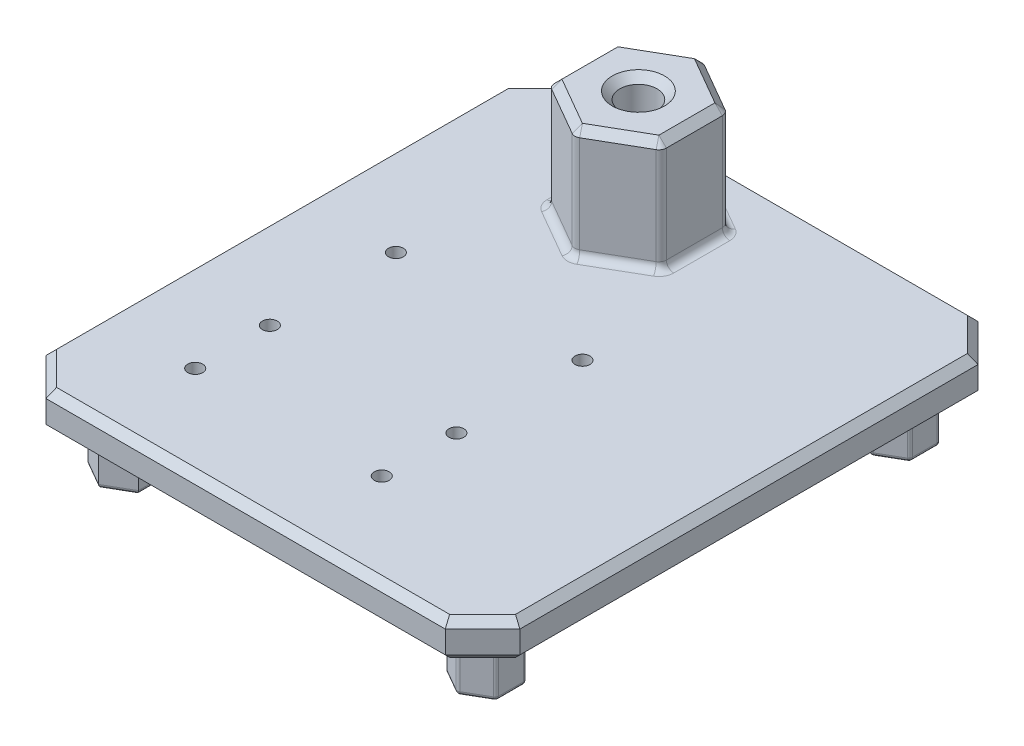
SolidWorks part; units mm, degrees
ref_plane "Front Plane" through (0, 0, 0) normal (0, 0, 1) x (1, 0, 0)
ref_plane "Top Plane" through (0, 0, 0) normal (0, 1, 0) x (1, 0, 0)
ref_plane "Right Plane" through (0, 0, 0) normal (1, 0, 0) x (0, 0, -1)
sketch "Sketch2" plane through (0, 0, 0) normal (0, 1, 0) x (1, 0, 0)
  line L1 (0, -17.3205) -> (15, -8.6603)
  line L2 (15, -8.6603) -> (15, 8.6603)
  line L3 (15, 8.6603) -> (0, 17.3205)
  line L4 (0, 17.3205) -> (-15, 8.6603)
  line L5 (-15, 8.6603) -> (-15, -8.6603)
  line L6 (-15, -8.6603) -> (0, -17.3205)
  circle A0 centre (0, 0) radius 15 construction
  circle A1 centre (0, 0) radius 5
  dimension "D2" = 10
  dimension "D1" = 30
extrude "Boss-Extrude1" add sketch "Sketch2" along normal blind 30
sketch "Sketch4" plane through (0, 0, 0) normal (0, 1, 0) x (1, 0, 0)
  line L0 (-40, 24.0027) -> (-50, 14.0027)
  line L1 (-40, 24.0027) -> (67.0218, 24.0027)
  line L2 (-50, 14.0027) -> (-50, -108.7974)
  line L3 (-40, -118.7974) -> (67.0218, -118.7974)
  line L4 (77.0218, 14.0027) -> (77.0218, -108.7974)
  line L5 (-50, 24.0027) -> (77.0218, -118.7974) construction
  line L6 (-50, -118.7974) -> (77.0218, 24.0027) construction
  line L7 (67.0218, 24.0027) -> (77.0218, 14.0027)
  line L8 (67.0218, -118.7974) -> (77.0218, -108.7974)
  line L9 (-50, -108.7974) -> (-40, -118.7974)
  point P0 (13.5109, -47.3973)
  dimension "D1" = 50
extrude "Boss-Extrude2" add sketch "Sketch4" against normal blind 10 contours L2 L9 L3 L8 L4 L7 L1 L0
sketch "Sketch5" plane through (0, 0, 0) normal (0, 1, 0) x (1, 0, 0)
  line L0 (-40, -118.7974) -> (67.0218, -118.7974) construction
  line L1 (-25, -93.7974) -> (-25, -7.9597) construction
  point P0 (-25, -40)
  point P1 (25, -40)
  point P4 (-25, -73.7974)
  point P6 (-25, -93.7974)
  point P8 (25, -73.7974)
  point P10 (25, -93.7974)
  dimension "D1" = 50
  dimension "D2" = 25
  dimension "D3" = 40
  dimension "D4" = 25
  dimension "D5" = 45
hole_wizard "Ø4.0mm Dowel Hole1" positions "Sketch5" profile "Sketch6" hole size "Ø4.0" standard "ISO"
sketch "Sketch6" plane through (-25, 0, 40) normal (1, 0, 0) x (0, 0, 1)
  line L0 (0, 0) -> (0, 11.2017)
  line L1 (0, 11.2017) -> (2, 10)
  line L2 (2, 10) -> (2, 0)
  line L5 (2, 0) -> (0, 0)
  line L10 (0, 11.2017) -> (-2, 10) construction
  line L11 (0, -6.35) -> (0, 107.95) construction
  dimension "Hole Dia." = 4
  dimension "Hole Depth" = 10
  dimension "Drill Angle" = 118
fillet "Fillet1" radius 2 12 edges at (-7.5, 0, -12.9904) (-15, 0, 0) (7.5, 0, -12.9904) (-7.5, 0, 12.9904) (15, 0, 0) (7.5, 0, 12.9904) (15, 15, -8.6603) (0, 15, -17.3205) (-15, 15, -8.6603) (-15, 15, 8.6603) (0, 15, 17.3205) (15, 15, 8.6603)
chamfer "Chamfer1" distance 2 angle 45 12 edges at (7.5, 30, -12.9904) (0, 30, -17.0111) (14.7321, 30, -8.5056) (-7.5, 30, -12.9904) (15, 30, 0) (-14.7321, 30, -8.5056) (14.7321, 30, 8.5056) (-15, 30, 0) (7.5, 30, 12.9904) (-14.7321, 30, 8.5056) (0, 30, 17.0111) (-7.5, 30, 12.9904)
chamfer "Chamfer2" distance 2 angle 45 1 edges at (0, 30, 5)
sketch "Sketch7" plane through (0, -10, 0) normal (0, -1, 0) x (1, 0, 0)
  line L0 (-50, -14.0027) -> (-50, 108.7974) construction
  line L1 (-28.25, -12.3225) -> (-28.25, -5.683)
  line L2 (-28.75, -4.8169) -> (-34.5, -1.4972)
  line L3 (-35.5, -1.4972) -> (-41.25, -4.8169)
  line L4 (-41.75, -5.683) -> (-41.75, -12.3225)
  line L5 (-41.25, -13.1885) -> (-35.5, -16.5083)
  line L6 (-34.5, -16.5083) -> (-28.75, -13.1885)
  line L7 (67.75, -12.3225) -> (67.75, -5.683)
  line L8 (67.25, -4.8169) -> (61.5, -1.4972)
  line L9 (60.5, -1.4972) -> (54.75, -4.8169)
  line L10 (54.25, -5.683) -> (54.25, -12.3225)
  line L11 (54.75, -13.1885) -> (60.5, -16.5083)
  line L12 (61.5, -16.5083) -> (67.25, -13.1885)
  line L13 (67.75, 98.5575) -> (67.75, 105.197)
  line L14 (67.25, 106.0631) -> (61.5, 109.3828)
  line L15 (60.5, 109.3828) -> (54.75, 106.0631)
  line L16 (54.25, 105.197) -> (54.25, 98.5575)
  line L17 (54.75, 97.6915) -> (60.5, 94.3717)
  line L18 (61.5, 94.3717) -> (67.25, 97.6915)
  line L19 (-40, -24.0027) -> (67.0218, -24.0027) construction
  line L21 (-35, 94.083) -> (-28.25, 97.9802)
  line L22 (-28.25, 97.9802) -> (-28.25, 105.7744)
  line L23 (-28.25, 105.7744) -> (-35, 109.6715)
  line L24 (-35, 109.6715) -> (-41.75, 105.7744)
  line L25 (-41.75, 105.7744) -> (-41.75, 97.9802)
  line L26 (-41.75, 97.9802) -> (-35, 94.083)
  circle A0 centre (-35, -9.0027) radius 6.75 construction
  circle A1 centre (61, -9.0027) radius 6.75 construction
  circle A2 centre (61, 101.8773) radius 6.75 construction
  arc A3 (67.75, 98.5575) -> (67.25, 97.6915) centre (66.75, 98.5575) cw
  arc A4 (60.5, 94.3717) -> (61.5, 94.3717) centre (61, 95.2377) ccw
  arc A5 (54.25, 98.5575) -> (54.75, 97.6915) centre (55.25, 98.5575) ccw
  arc A6 (54.75, 106.0631) -> (54.25, 105.197) centre (55.25, 105.197) ccw
  arc A7 (61.5, 109.3828) -> (60.5, 109.3828) centre (61, 108.5168) ccw
  arc A8 (67.75, -5.683) -> (67.25, -4.8169) centre (66.75, -5.683) ccw
  arc A9 (67.75, -12.3225) -> (67.25, -13.1885) centre (66.75, -12.3225) cw
  arc A10 (60.5, -16.5083) -> (61.5, -16.5083) centre (61, -15.6423) ccw
  arc A11 (54.25, -12.3225) -> (54.75, -13.1885) centre (55.25, -12.3225) ccw
  arc A12 (54.75, -4.8169) -> (54.25, -5.683) centre (55.25, -5.683) ccw
  arc A13 (61.5, -1.4972) -> (60.5, -1.4972) centre (61, -2.3632) ccw
  arc A14 (-28.25, -5.683) -> (-28.75, -4.8169) centre (-29.25, -5.683) ccw
  arc A15 (-28.25, -12.3225) -> (-28.75, -13.1885) centre (-29.25, -12.3225) cw
  arc A16 (-35.5, -16.5083) -> (-34.5, -16.5083) centre (-35, -15.6423) ccw
  arc A17 (-41.75, -12.3225) -> (-41.25, -13.1885) centre (-40.75, -12.3225) ccw
  arc A18 (-41.25, -4.8169) -> (-41.75, -5.683) centre (-40.75, -5.683) ccw
  arc A19 (-34.5, -1.4972) -> (-35.5, -1.4972) centre (-35, -2.3632) ccw
  arc A20 (67.75, 105.197) -> (67.25, 106.0631) centre (66.75, 105.197) ccw
  circle A21 centre (-35, 101.8773) radius 6.75 construction
  dimension "D6" = 1
  dimension "D7" = 1
  dimension "D1" = 13.5
  dimension "D2" = 96
  dimension "D3" = 110.88
  dimension "D4" = 15
  dimension "D5" = 15
extrude "Boss-Extrude3" add sketch "Sketch7" along normal blind 15
chamfer "Chamfer3" distance 0.5 angle 45 42 edges at (54.25, -10, 101.8773) (54.384, -10, 98.0575) (54.384, -10, 105.697) (57.625, -10, 96.0316) (57.625, -10, 107.7229) (61, -10, 94.2377) (61, -10, 109.5168) (64.375, -10, 96.0316) (64.375, -10, 107.7229) (67.616, -10, 98.0575) (67.616, -10, 105.697) (67.75, -10, 101.8773) (-31.625, -10, 107.7229) (-28.25, -10, 101.8773) (-31.625, -10, 96.0316) (-38.375, -10, 96.0316) (-38.375, -10, 107.7229) (-41.75, -10, 101.8773) (67.75, -10, -9.0027) (67.616, -10, -5.183) (67.616, -10, -12.8225) (64.375, -10, -3.1571) (64.375, -10, -14.8484) (61, -10, -1.3632) (61, -10, -16.6423) (57.625, -10, -3.1571) (57.625, -10, -14.8484) (54.384, -10, -5.183) (54.384, -10, -12.8225) (54.25, -10, -9.0027) (-31.625, -10, -14.8484) (-28.384, -10, -12.8225) (-35, -10, -16.6423) (-28.25, -10, -9.0027) (-38.375, -10, -14.8484) (-28.384, -10, -5.183) (-41.616, -10, -12.8225) (-31.625, -10, -3.1571) (-41.75, -10, -9.0027) (-35, -10, -1.3632) (-41.616, -10, -5.183) (-38.375, -10, -3.1571)
chamfer "Chamfer4" distance 2 angle 45 16 edges at (-45, -10, -19.0027) (13.5109, -10, -24.0027) (72.0218, -10, -19.0027) (-50, -10, 47.3973) (-45, -10, 113.7974) (13.5109, -10, 118.7974) (72.0218, -10, 113.7974) (77.0218, -10, 47.3973) (72.0218, 0, -19.0027) (13.5109, 0, -24.0027) (-45, 0, -19.0027) (-50, 0, 47.3973) (-45, 0, 113.7974) (13.5109, 0, 118.7974) (77.0218, 0, 47.3973) (72.0218, 0, 113.7974)
sketch "Sketch8" plane through (0, -25, 0) normal (0, -1, 0) x (1, 0, 0)
  point P0 (-35, 101.8773)
  point P1 (61, 101.8773)
  point P3 (61, -9.0027)
  point P5 (-35, -9.0027)
hole_wizard "Ø4.0mm Dowel Hole2" positions "Sketch8" profile "Sketch9" hole size "Ø4.0" standard "ISO"
sketch "Sketch9" plane through (-35, -25, 101.8773) normal (1, 0, 0) x (0, 0, -1)
  line L0 (0, 0) -> (0, 16.2017)
  line L1 (0, 16.2017) -> (2, 15)
  line L2 (2, 15) -> (2, 0)
  line L5 (2, 0) -> (0, 0)
  line L10 (0, 16.2017) -> (-2, 15) construction
  line L11 (0, -6.35) -> (0, 107.95) construction
  dimension "Hole Dia." = 4
  dimension "Hole Depth" = 15
  dimension "Drill Angle" = 118
fillet "Fillet2" radius 1 42 edges at (-38.375, -25, -3.1571) (-35, -25, -1.3632) (-31.625, -25, -3.1571) (-28.384, -25, -5.183) (-28.25, -25, -9.0027) (-28.384, -25, -12.8225) (-31.625, -25, -14.8484) (-35, -25, -16.6423) (-38.375, -25, -14.8484) (-41.616, -25, -12.8225) (-41.75, -25, -9.0027) (57.625, -25, -3.1571) (61, -25, -1.3632) (64.375, -25, -3.1571) (67.616, -25, -5.183) (67.75, -25, -9.0027) (67.616, -25, -12.8225) (64.375, -25, -14.8484) (61, -25, -16.6423) (57.625, -25, -14.8484) (54.384, -25, -12.8225) (54.25, -25, -9.0027) (54.384, -25, 105.697) (57.625, -25, 107.7229) (61, -25, 109.5168) (64.375, -25, 107.7229) (67.616, -25, 105.697) (67.75, -25, 101.8773) (67.616, -25, 98.0575) (64.375, -25, 96.0316) (61, -25, 94.2377) (57.625, -25, 96.0316) (54.384, -25, 98.0575) (-41.616, -25, -5.183) (54.384, -25, -5.183) (54.25, -25, 101.8773) (-31.625, -25, 107.7229) (-28.25, -25, 101.8773) (-31.625, -25, 96.0316) (-38.375, -25, 96.0316) (-41.75, -25, 101.8773) (-38.375, -25, 107.7229)
